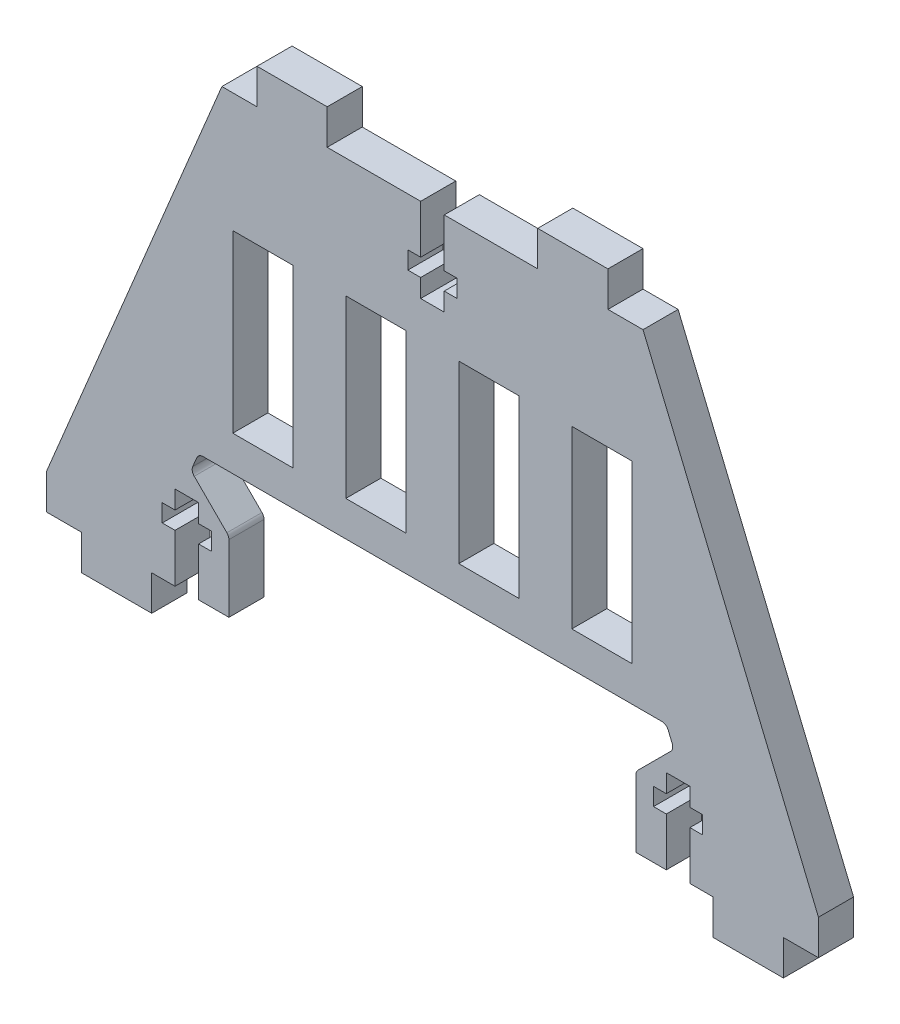
SolidWorks part; units mm, degrees
ref_plane "Front Plane" through (0, 0, 0) normal (0, 0, 1) x (1, 0, 0)
ref_plane "Top Plane" through (0, 0, 0) normal (0, 1, 0) x (1, 0, 0)
ref_plane "Right Plane" through (0, 0, 0) normal (1, 0, 0) x (0, 0, -1)
sketch "Sketch1" plane through (0, 0, 0) normal (0, 0, 1) x (1, 0, 0)
  line L1 (-69.85, 41.275) -> (69.85, 41.275)
  line L2 (-69.85, 41.275) -> (-69.85, -41.275)
  line L3 (-69.85, -41.275) -> (69.85, -41.275)
  line L4 (69.85, 41.275) -> (69.85, -41.275)
  line L5 (-69.85, 41.275) -> (69.85, -41.275) construction
  line L6 (-69.85, -41.275) -> (69.85, 41.275) construction
  point P0 (0, 0)
  dimension "D1" = 82.55
  dimension "D2" = 139.7
extrude "Boss-Extrude1" add sketch "Sketch1" along normal blind 6.35
sketch "Sketch2" plane through (0, 0, 0) normal (0, 0, -1) x (-1, 0, 0)
  line L0 (69.85, -41.275) -> (-69.85, -41.275) construction
  line L1 (-63.5, -41.275) -> (-50.8, -41.275)
  line L2 (-63.5, -41.275) -> (-63.5, -47.625)
  line L3 (-63.5, -47.625) -> (-50.8, -47.625)
  line L4 (-50.8, -41.275) -> (-50.8, -47.625)
  line L5 (-69.85, -41.275) -> (-69.85, 41.275) construction
  line L6 (-69.85, 41.275) -> (69.85, 41.275) construction
  line L7 (-31.75, 41.275) -> (-19.05, 41.275)
  line L8 (-31.75, 41.275) -> (-31.75, 47.625)
  line L9 (-31.75, 47.625) -> (-19.05, 47.625)
  line L10 (-19.05, 41.275) -> (-19.05, 47.625)
  dimension "D1" = 6.35
  dimension "D2" = 12.7
  dimension "D3" = 6.35
  dimension "D4" = 6.35
  dimension "D5" = 12.7
  dimension "D6" = 38.1
extrude "Boss-Extrude2" add sketch "Sketch2" against normal blind 6.35
sketch "Sketch3" plane through (0, 0, 0) normal (0, 0, -1) x (-1, 0, 0)
  line L1 (-46.5836, -41.275) -> (-46.5836, -32.512)
  line L2 (69.85, -41.275) -> (-50.8, -41.275) construction
  line L3 (-46.5836, -32.512) -> (-48.895, -32.512)
  line L4 (-48.895, -32.512) -> (-48.895, -29.337)
  line L5 (-48.895, -29.337) -> (-46.5836, -29.337)
  line L6 (-46.5836, -29.337) -> (-46.5836, -26.035)
  line L7 (-46.5836, -26.035) -> (-42.3164, -26.035)
  line L8 (-44.45, -26.035) -> (-44.45, -41.275) construction
  line L9 (-42.3164, -41.275) -> (-46.5836, -41.275)
  line L10 (-63.5, -47.625) -> (-50.8, -47.625) construction
  line L11 (-42.3164, -29.337) -> (-42.3164, -26.035)
  line L12 (-40.005, -29.337) -> (-42.3164, -29.337)
  line L13 (-40.005, -32.512) -> (-40.005, -29.337)
  line L14 (-42.3164, -32.512) -> (-40.005, -32.512)
  line L15 (-42.3164, -41.275) -> (-42.3164, -32.512)
  line L16 (-50.8, -47.625) -> (-50.8, -41.275) construction
  dimension "D1" = 21.59
  dimension "D2" = 3.302
  dimension "D3" = 3.175
  dimension "D4" = 4.2672
  dimension "D5" = 4.445
  dimension "D6" = 6.35
extrude "Cut-Extrude1" cut sketch "Sketch3" against normal blind 6.35
sketch "Sketch7" plane through (0, 0, 0) normal (0, 0, -1) x (-1, 0, 0)
  line L0 (-38.1, 41.275) -> (-69.85, -34.925)
  line L1 (-69.85, 41.275) -> (-31.75, 41.275) construction
  line L2 (-69.85, -41.275) -> (-69.85, 41.275) construction
  line L3 (-69.85, -34.925) -> (-69.85, 41.275)
  line L4 (-69.85, 41.275) -> (-38.1, 41.275)
  line L5 (-31.75, 47.625) -> (-31.75, 41.275) construction
  dimension "D1" = 6.35
  dimension "D2" = 6.35
extrude "Cut-Extrude8" cut sketch "Sketch7" against normal blind 6.35
mirror "Mirror2" about plane through (0, 0, 0) normal (1, 0, 0) of "Cut-Extrude8", "Boss-Extrude2"
mirror "Mirror4" about plane through (0, 0, 0) normal (1, 0, 0) of "Cut-Extrude1"
sketch "Sketch4" plane through (0, 0, 0) normal (0, 0, -1) x (-1, 0, 0)
  line L0 (0, 41.275) -> (0, 0) construction
  line L2 (2.1336, 41.275) -> (-2.1336, 41.275)
  line L3 (-2.1336, 41.275) -> (-2.1336, 32.512)
  line L4 (-2.1336, 32.512) -> (-4.445, 32.512)
  line L5 (-4.445, 32.512) -> (-4.445, 29.337)
  line L6 (-4.445, 29.337) -> (-2.1336, 29.337)
  line L7 (-2.1336, 29.337) -> (-2.1336, 26.035)
  line L8 (-2.1336, 26.035) -> (2.1336, 26.035)
  line L10 (2.1336, 29.337) -> (2.1336, 26.035)
  line L11 (4.445, 29.337) -> (2.1336, 29.337)
  line L12 (4.445, 32.512) -> (4.445, 29.337)
  line L13 (2.1336, 32.512) -> (4.445, 32.512)
  line L14 (2.1336, 41.275) -> (2.1336, 32.512)
  line L15 (-19.05, 47.625) -> (-31.75, 47.625) construction
  line L16 (-19.05, 41.275) -> (19.05, 41.275) construction
  point P15 (0, 26.035)
  dimension "D1" = 2.1336
  dimension "D2" = 4.445
  dimension "D3" = 21.59
  dimension "D4" = 3.302
  dimension "D5" = 3.175
extrude "Cut-Extrude2" cut sketch "Sketch4" against normal blind 6.35
sketch "Sketch8" plane through (0, 0, 6.35) normal (0, 0, 1) x (1, 0, 0)
  line L0 (-36.83, -28.575) -> (-43.7029, -21.7021)
  line L1 (36.83, -28.575) -> (43.7029, -21.7021)
  line L6 (-69.85, -34.925) -> (-38.1, 41.275) construction
  line L8 (69.85, -34.925) -> (38.1, 41.275) construction
  line L9 (-42.3164, -41.275) -> (42.3164, -41.275) construction
  line L10 (-69.85, -34.925) -> (-38.1, 41.275) construction
  line L11 (-36.83, -28.575) -> (-36.83, -41.275)
  line L12 (69.85, -34.925) -> (38.1, 41.275) construction
  line L13 (-36.83, -41.275) -> (36.83, -41.275)
  line L14 (-43.7029, -21.7021) -> (-42.3333, -18.415)
  line L15 (-42.3333, -18.415) -> (42.3333, -18.415)
  line L16 (2.1336, 26.035) -> (-2.1336, 26.035) construction
  line L17 (-52.2654, -42.2519) -> (-20.5154, 33.9481) construction
  line L18 (52.2654, -42.2519) -> (20.5154, 33.9481) construction
  line L19 (36.83, -28.575) -> (36.83, -41.275)
  line L20 (43.7029, -21.7021) -> (42.3333, -18.415)
  line L22 (40.005, -32.512) -> (40.005, -29.337) construction
  line L23 (-40.005, -32.512) -> (-40.005, -29.337) construction
  point P16 (40.005, -30.9245)
  dimension "D3" = 44.45
  dimension "D4" = 3.175
  dimension "D5" = 3.175
  dimension "D8" = 12.7
  dimension "D9" = 225
  dimension "D1" = 19.05
  dimension "D2" = 19.05
extrude "Cut-Extrude9" cut sketch "Sketch8" against normal through all and the other way through all
fillet "Fillet1" radius 1.27 6 edges at (36.83, -28.575, 3.175) (43.7029, -21.7021, 3.175) (42.3333, -18.415, 3.175) (-42.3333, -18.415, 3.175) (-43.7029, -21.7021, 3.175) (-36.83, -28.575, 3.175)
sketch "Sketch9" plane through (0, 0, 6.35) normal (0, 0, 1) x (1, 0, 0)
  line L0 (-63.61, 3.81) -> (64.3051, 3.81) construction
  line L1 (-36.1315, 19.685) -> (-25.2095, 19.685)
  line L2 (-36.1315, 19.685) -> (-36.1315, -12.065)
  line L3 (-36.1315, -12.065) -> (-25.2095, -12.065)
  line L4 (-25.2095, 19.685) -> (-25.2095, -12.065)
  line L5 (-15.6845, 19.685) -> (-4.7625, 19.685)
  line L6 (-15.6845, 19.685) -> (-15.6845, -12.065)
  line L7 (-15.6845, -12.065) -> (-4.7625, -12.065)
  line L8 (-4.7625, 19.685) -> (-4.7625, -12.065)
  line L9 (4.7625, 19.685) -> (15.6845, 19.685)
  line L10 (4.7625, 19.685) -> (4.7625, -12.065)
  line L11 (4.7625, -12.065) -> (15.6845, -12.065)
  line L12 (15.6845, 19.685) -> (15.6845, -12.065)
  line L13 (25.2095, 19.685) -> (36.1315, 19.685)
  line L14 (25.2095, 19.685) -> (25.2095, -12.065)
  line L15 (25.2095, -12.065) -> (36.1315, -12.065)
  line L16 (36.1315, 19.685) -> (36.1315, -12.065)
  line L17 (0, 0) -> (0, 50.0032) construction
  line L18 (2.1336, 26.035) -> (-2.1336, 26.035) construction
  line L19 (41.4867, -18.415) -> (-41.4867, -18.415) construction
  line L20 (-25.2095, 19.685) -> (-15.6845, 19.685) construction
  line L21 (-4.7625, 19.685) -> (4.7625, 19.685) construction
  dimension "D1" = 10.922
  dimension "D2" = 31.75
  dimension "D3" = 9.525
extrude "Switches Cut" cut sketch "Sketch9" against normal through all
